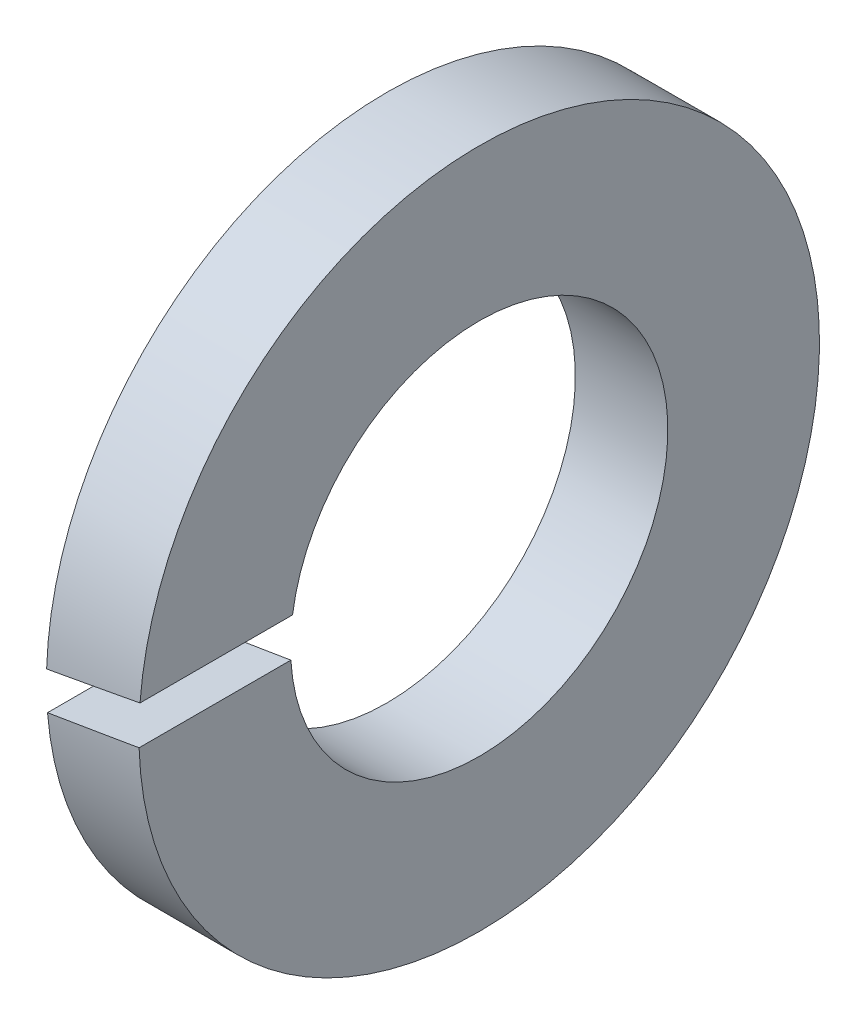
SolidWorks part; units mm, degrees
ref_plane "前视基准面" through (0, 0, 0) normal (0, 0, 1) x (1, 0, 0)
ref_plane "上视基准面" through (0, 0, 0) normal (0, 1, 0) x (1, 0, 0)
ref_plane "右视基准面" through (0, 0, 0) normal (1, 0, 0) x (0, 0, -1)
sketch "草图1" plane through (0, 0, 0) normal (0, 0, 1) x (1, 0, 0)
  line L0 (-1.25, 5.1) -> (1.25, 5.1)
  line L1 (1.25, 5.1) -> (1.25, 9.2)
  line L2 (1.25, 9.2) -> (-1.25, 9.2)
  line L3 (-1.25, 9.2) -> (-1.25, 5.1)
  line L4 (1.25, 0) -> (-1.25, 0) construction
revolve "旋转1" add sketch "草图1" angle 360 about L4
sketch "草图2" plane through (0, 0, 0) normal (0, 0, 1) x (1, 0, 0)
  line L0 (-2.5506, 0.0681) -> (-2.3735, -0.9364)
  line L1 (-2.3735, -0.9364) -> (2.5506, -0.0681)
  line L2 (2.5506, -0.0681) -> (2.3735, 0.9364)
  line L3 (2.3735, 0.9364) -> (-2.5506, 0.0681)
extrude "切除-拉伸1" cut sketch "草图2" along normal blind 18.4
ref_plane "基准面4" through (1.25, 0, 0) normal (1, 0, 0) x (0, 0, -1)
ref_plane "基准面5" through (-1.25, 0, 0) normal (1, 0, 0) x (0, 0, -1)
ref_plane "spring_washer_to_bolt XY" through (0, 0, 0) normal (1, 0, 0) x (0, 0, -1)
ref_plane "spring_washer_to_bolt XZ" through (0, 0, 0) normal (0, -1, 0) x (-1, 0, 0)
ref_plane "spring_washer_to_bolt YZ" through (0, 0, 0) normal (0, 0, -1) x (-1, 0, 0)
ref_axis "spring_washer_to_bolt X" through (0, 0, 80.9) along (0, 0, -1)
ref_axis "spring_washer_to_bolt Y" through (0, -50, 0) along (0, 1, 0)
ref_axis "spring_washer_to_bolt Z" through (80.9, 0, 0) along (-1, 0, 0)
sketch3d "spring_washer_to_bolt"
  point P0 (0, 0, 0)
ref_plane "to_bolt XY" through (1.25, 0, 0) normal (1, 0, 0) x (0, 0, -1)
ref_plane "to_bolt XZ" through (0, 0, 0) normal (0, -1, 0) x (-1, 0, 0)
ref_plane "to_bolt YZ" through (0, 0, 0) normal (0, 0, -1) x (-1, 0, 0)
ref_axis "to_bolt X" through (1.25, 0, 80.9) along (0, 0, -1)
ref_axis "to_bolt Y" through (1.25, -50, 0) along (0, 1, 0)
ref_axis "to_bolt Z" through (80.9, 0, 0) along (-1, 0, 0)
sketch3d "to_bolt"
  point P0 (1.25, 0, 0)
ref_plane "to_washer XY" through (-1.25, 0, 0) normal (-1, 0, 0) x (0, 0, 1)
ref_plane "to_washer XZ" through (0, 0, 0) normal (0, 1, 0) x (1, 0, 0)
ref_plane "to_washer YZ" through (0, 0, 0) normal (0, 0, -1) x (-1, 0, 0)
ref_axis "to_washer X" through (-1.25, 0, 80.9) along (0, 0, -1)
ref_axis "to_washer Y" through (-1.25, 50, 0) along (0, -1, 0)
ref_axis "to_washer Z" through (-80.9, 0, 0) along (1, 0, 0)
sketch3d "to_washer"
  point P0 (-1.25, 0, 0)
